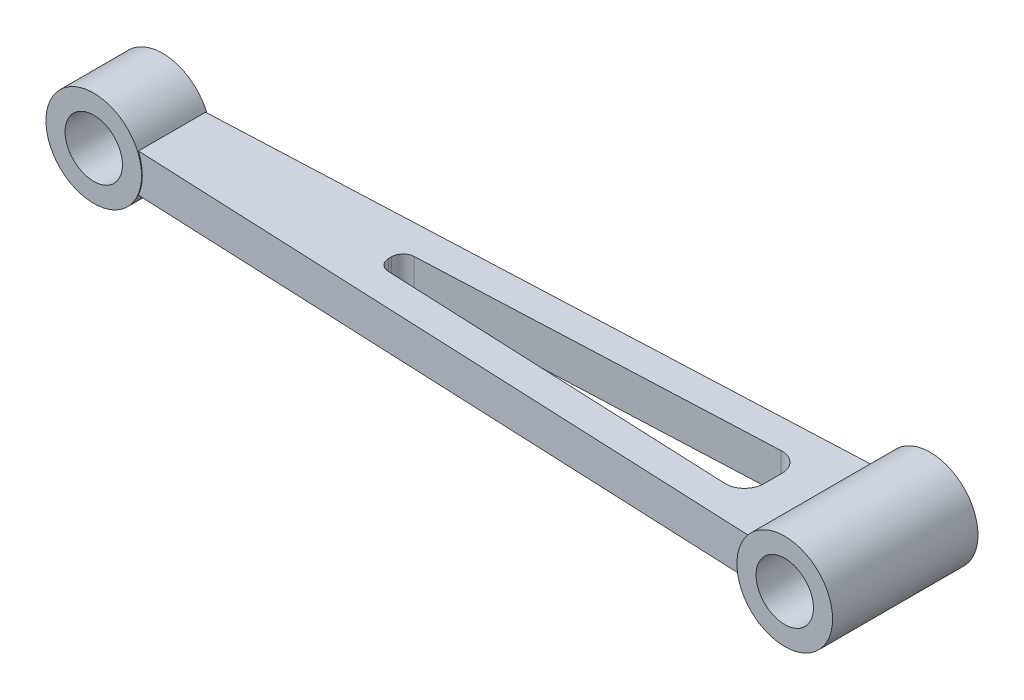
SolidWorks part; units mm, degrees
ref_plane "Front Plane" through (0, 0, 0) normal (0, 0, 1) x (1, 0, 0)
ref_plane "Top Plane" through (0, 0, 0) normal (0, 1, 0) x (1, 0, 0)
ref_plane "Right Plane" through (0, 0, 0) normal (1, 0, 0) x (0, 0, -1)
sketch "Sketch1" plane through (0, 0, 0) normal (0, 1, 0) x (1, 0, 0)
  line L0 (-84.78, 8.7305) -> (-84.78, 0)
  line L1 (-84.78, 0) -> (84.78, 0)
  line L2 (84.78, 0) -> (84.78, 16.1336)
  line L3 (84.78, 16.1336) -> (-84.78, 8.7305)
  line L4 (-100.7055, 45.5229) -> (-100.7055, -17.1586) construction
  line L5 (93.8545, 49.0246) -> (93.8545, -17.1586) construction
  line L6 (-26.8155, 0) -> (-26.8155, 0.3818)
  line L7 (-23.9464, 3.3789) -> (67.9664, 7.3919)
  line L8 (73.1845, 2.3967) -> (73.1845, 0)
  line L9 (73.1845, 0) -> (-26.8155, 0)
  line L10 (-26.8155, 39.5769) -> (-26.8155, -22.5329) construction
  line L11 (73.1845, -27.5495) -> (73.1845, 42.6824) construction
  arc A0 (-26.8155, 0.3818) -> (-23.9464, 3.3789) centre (-23.8155, 0.3818) cw
  arc A1 (67.9664, 7.3919) -> (73.1845, 2.3967) centre (68.1845, 2.3967) cw
  point P2 (-70.7055, 9.345)
  point P10 (73.1845, 15.6274)
  dimension "D11" = 3
  dimension "D12" = 5
  dimension "D13" = 26.8155
  dimension "D1" = 2.5
  dimension "D2" = 194.56
  dimension "D3" = 20.67
  dimension "D4" = 169.56
  dimension "D5" = 84.78
  dimension "D6" = 100.7055
  dimension "D7" = 30
  dimension "D8" = 9.345
  dimension "D9" = 8
  dimension "D10" = 100
  dimension "D14" = 27.5495
extrude "Boss-Extrude1" add sketch "Sketch1" along normal blind 10 contours L7 A1 L8 L1 L2 L3 L0 L6 A0 region at (1.1932, 0, -7.6182)
mirror "Mirror1" about plane through (0, 0, 0) normal (0, 0, 1) of "Boss-Extrude1"
sketch "Sketch2" plane through (0, 0, 0) normal (0, 0, 1) x (1, 0, 0)
  line L0 (-82.78, 35.6515) -> (-82.78, -16.7699) construction
  line L1 (-84.78, 10) -> (-84.78, 0) construction
  circle A0 centre (-95.28, 5) radius 12.5
  dimension "D2" = 25
  dimension "D1" = 5
  dimension "D3" = 2
extrude "Boss-Extrude2" add sketch "Sketch2" along normal blind 9 and the other way blind 9
sketch "Sketch3" plane through (0, 0, 9) normal (0, 0, 1) x (1, 0, 0)
  circle A0 centre (-95.28, 5) radius 7.5
  dimension "D1" = 15
extrude "Cut-Extrude1" cut sketch "Sketch3" against normal through all
sketch "Sketch4" plane through (0, 0, 0) normal (0, 0, 1) x (1, 0, 0)
  line L0 (82.78, 33.1047) -> (82.78, -20.7626) construction
  line L1 (84.78, 10) -> (84.78, 0) construction
  circle A0 centre (95.28, 5) radius 12.5
  dimension "D3" = 25
  dimension "D1" = 5
  dimension "D2" = 2
extrude "Boss-Extrude3" add sketch "Sketch4" along normal blind 19 and the other way blind 19
sketch "Sketch5" plane through (0, 0, 19) normal (0, 0, 1) x (1, 0, 0)
  circle A0 centre (95.28, 5) radius 7.5
  dimension "D1" = 15
extrude "Cut-Extrude2" cut sketch "Sketch5" against normal through all
